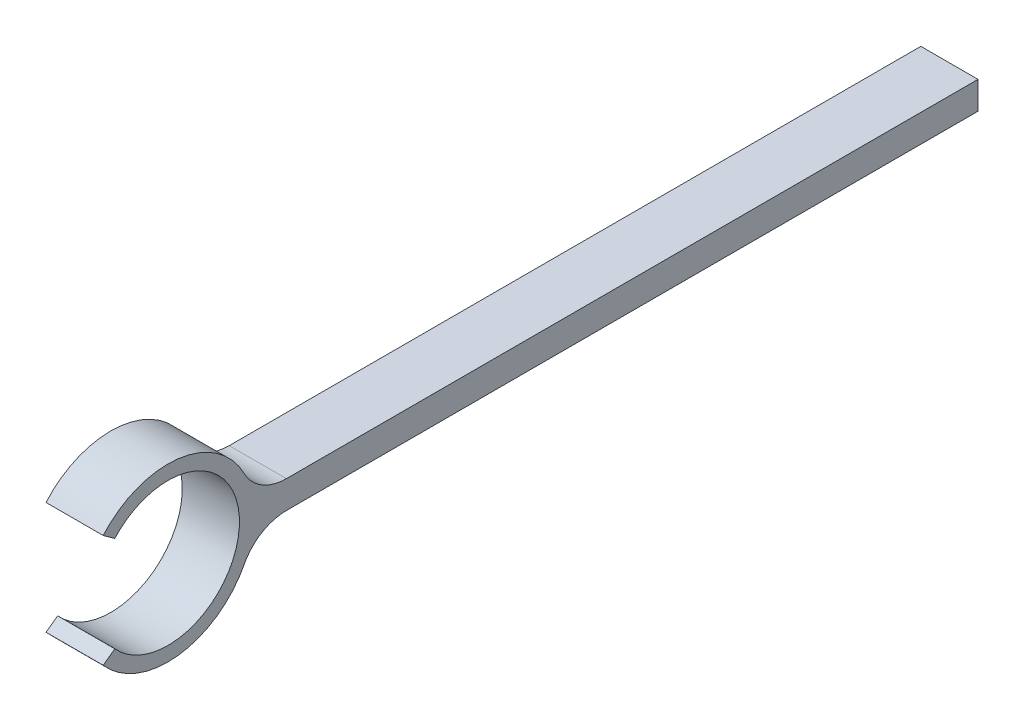
SolidWorks part; units mm, degrees
ref_plane "Front Plane" through (0, 0, 0) normal (0, 0, 1) x (1, 0, 0)
ref_plane "Top Plane" through (0, 0, 0) normal (0, 1, 0) x (1, 0, 0)
ref_plane "Right Plane" through (0, 0, 0) normal (1, 0, 0) x (0, 0, -1)
sketch "Sketch1" plane through (0, 0, 0) normal (1, 0, 0) x (0, 0, -1)
  line L0 (1.3952, 0) -> (-13.0645, 10.4065)
  line L1 (0, 0) -> (109.6696, 0) construction
  line L2 (8.8827, -1.4486) -> (85, -1.4486)
  line L3 (85, -1.4486) -> (85, 1.4486)
  line L4 (8.8827, 1.4486) -> (85, 1.4486)
  line L9 (15, 32.3322) -> (15, -32.3322) construction
  line L10 (1.3952, 0) -> (-13.0645, -10.4065)
  circle A0 centre (0, 0) radius 9
  circle A1 centre (0, 0) radius 7.5
  point P8 (25.0172, 0)
  point P14 (85, 0)
  point P18 (15, 0)
  dimension "D1" = 15
  dimension "D2" = 1.5
  dimension "D4" = 70
extrude "Boss-Extrude1" add sketch "Sketch1" along normal blind 6 contours A1 A0 | A0 region at (0, 5.6513, 6.0471) region at (0, 0, -46.9805)
fillet "Fillet1" radius 5 2 edges at (3, 1.4486, -8.8827) (3, -1.4486, -8.8827)
